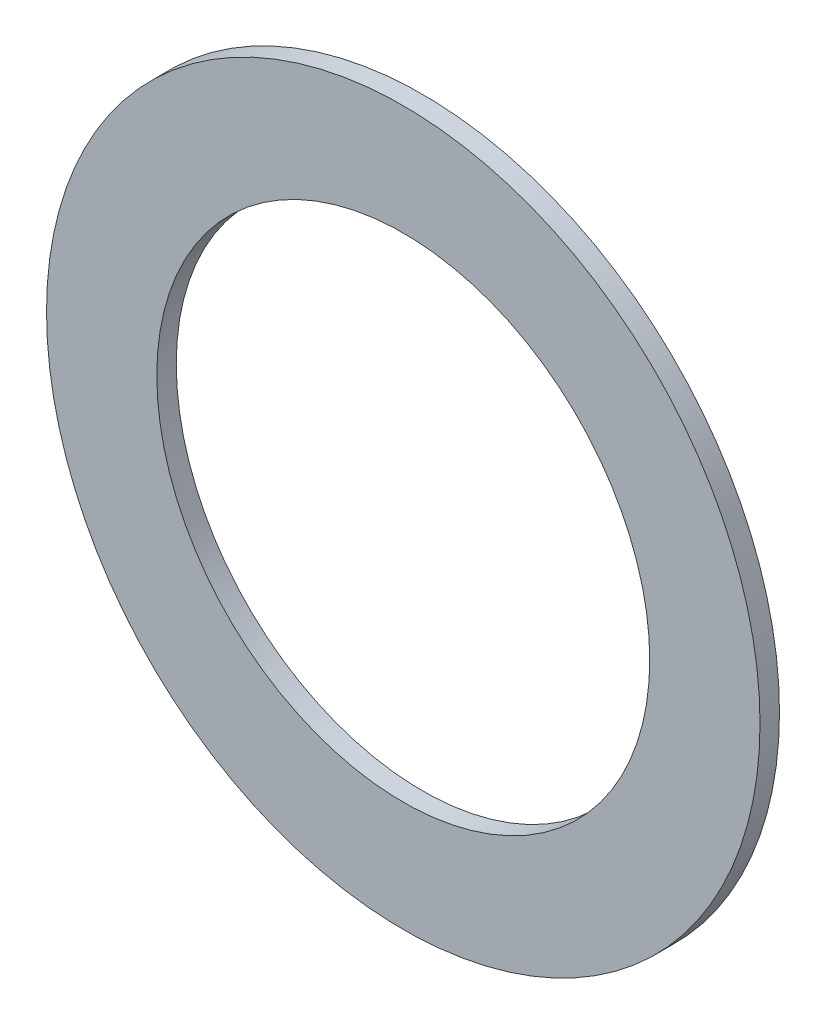
SolidWorks part; units mm, degrees
material "1.4301 (X5CrNi18-10)"
ref_plane "E_Rechts" through (0, 0, 0) normal (0, 0, 1) x (1, 0, 0)
ref_plane "E_Oben" through (0, 0, 0) normal (0, 1, 0) x (1, 0, 0)
ref_plane "E_Vorne" through (0, 0, 0) normal (1, 0, 0) x (0, 0, -1)
ref_axis "A_Drehachse" through (0, 0, -88.99) along (0, 0, 1)
sketch "Skizze1" plane through (0, 0, 0) normal (0, 0, 1) x (1, 0, 0)
  circle A0 centre (0, 0) radius 19
  circle A1 centre (0, 0) radius 27.5
extrude "Aufsatz-Linear austragen1" add sketch "Skizze1" along normal mid plane 1.5
